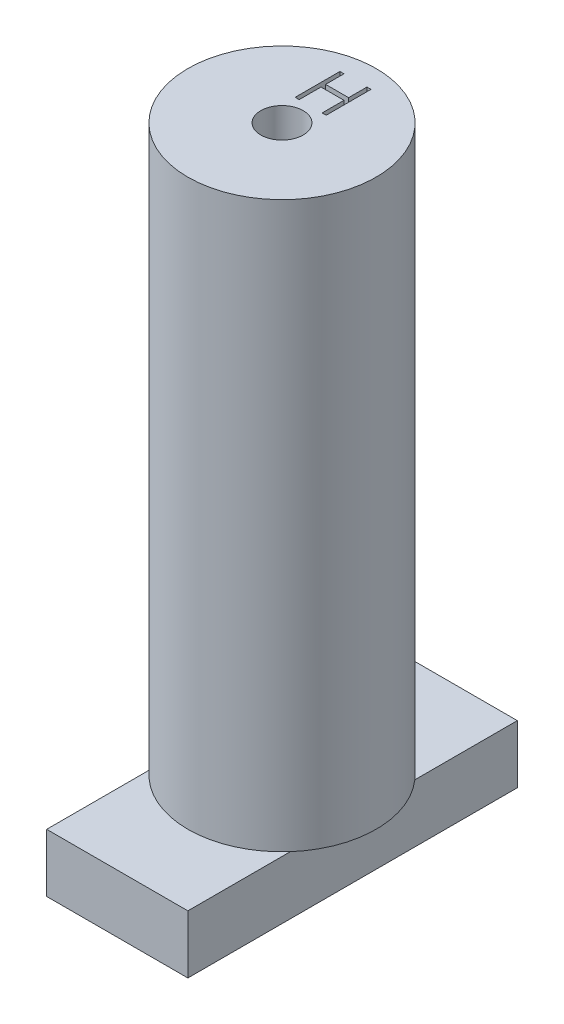
SolidWorks part; units mm, degrees
ref_plane "Front Plane" through (0, 0, 0) normal (0, 0, 1) x (1, 0, 0)
ref_plane "Top Plane" through (0, 0, 0) normal (0, 1, 0) x (1, 0, 0)
ref_plane "Right Plane" through (0, 0, 0) normal (1, 0, 0) x (0, 0, -1)
sketch "Sketch1" plane through (0, 0, 0) normal (0, 1, 0) x (1, 0, 0)
  circle A0 centre (0, 0) radius 10
  dimension "D1" = 20
extrude "Boss-Extrude1" add sketch "Sketch1" along normal blind 4
sketch "Sketch2" plane through (0, 4, 0) normal (0, 1, 0) x (1, 0, 0)
  circle A1 centre (0, 0) radius 3.5
  circle A2 centre (0, 0) radius 8
  circle A3 centre (0, 0) radius 8
  circle A4 centre (0, 0) radius 10 construction
  circle A5 centre (0, 0) radius 10
  circle M2 centre (0, 0) radius 10
  dimension "D2" = 7
  dimension "D1" = 2
extrude "Boss-Extrude2" add sketch "Sketch2" along normal blind 52 contours A1 | A3 M2 region at (0, 4, 0) region at (-9.7172, 4, 0)
sketch "Sketch3" plane through (0, 56, 0) normal (0, 1, 0) x (1, 0, 0)
  circle A0 centre (0, 0) radius 10 construction
  circle A1 centre (0, 0) radius 10
extrude "Boss-Extrude3" add sketch "Sketch3" along normal blind 4
sketch "Sketch4" plane through (0, 60, 0) normal (0, 1, 0) x (1, 0, 0)
  line L0 (-9.5253, 3.0445) -> (9.5253, 3.0445) construction
  circle A0 centre (0, 0) radius 10 construction
  text T0 "H" font "Century Gothic" height in points 18
extrude "Cut-Extrude1" cut sketch "Sketch4" against normal blind 2
sketch "Sketch5" plane through (0, 60, 0) normal (0, 1, 0) x (1, 0, 0)
  circle A0 centre (0, 0) radius 2.25
  dimension "D1" = 4.5
extrude "Cut-Extrude2" cut sketch "Sketch5" against normal blind 50
sketch "Sketch6" plane through (0, 0, 0) normal (0, -1, 0) x (1, 0, 0)
  line L0 (-10, 0) -> (10, 0) construction
  line L1 (-7.5, 17.5) -> (7.5, 17.5)
  line L2 (-7.5, 17.5) -> (-7.5, -17.5)
  line L3 (-7.5, -17.5) -> (7.5, -17.5)
  line L4 (7.5, 17.5) -> (7.5, -17.5)
  line L5 (-7.5, 0) -> (7.5, 0) construction
  line L6 (0, 17.5) -> (0, -17.5) construction
  line L7 (0, 10) -> (0, -10) construction
  circle A0 centre (0, 0) radius 10 construction
  dimension "D1" = 15
  dimension "D2" = 35
extrude "Boss-Extrude4" add sketch "Sketch6" along normal blind 6.18
sketch "Sketch7" plane through (0, -6.18, 0) normal (0, -1, 0) x (1, 0, 0)
  line L0 (0, 17.5) -> (0, -17.5) construction
  line L1 (7.5, 17.5) -> (-7.5, 17.5) construction
  line L2 (-7.5, -17.5) -> (7.5, -17.5) construction
  line L3 (-7.5, 0) -> (7.5, 0) construction
  line L4 (-7.5, 17.5) -> (-7.5, -17.5) construction
  line L5 (7.5, -6.6144) -> (7.5, 6.6144) construction
  line L6 (-1.59, 0) -> (1.59, 0) construction
  line L7 (-1.59, 6.5) -> (1.59, 6.5)
  line L8 (-1.59, 6.5) -> (-1.59, -6.5)
  line L9 (-1.59, -6.5) -> (1.59, -6.5)
  line L10 (1.59, 6.5) -> (1.59, -6.5)
  line L11 (0, 6.5) -> (0, -6.5) construction
  dimension "D1" = 3.18
  dimension "D2" = 13
extrude "Cut-Extrude3" cut sketch "Sketch7" against normal blind 4.18
